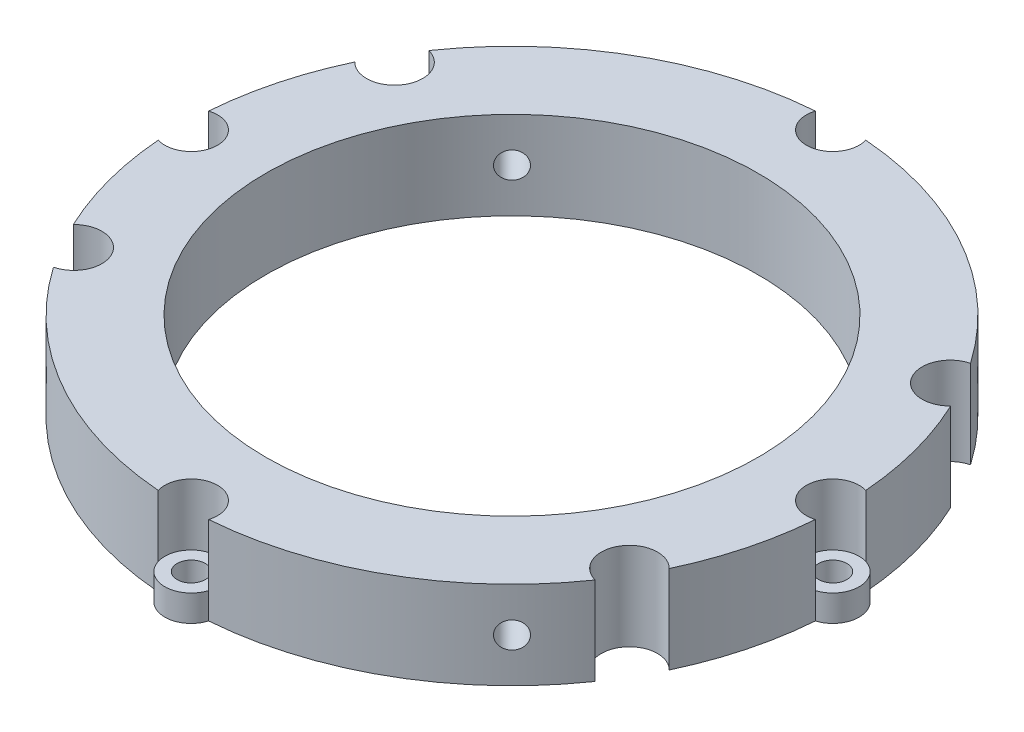
SolidWorks part; units mm, degrees
ref_plane "Ön Düzlem" through (0, 0, 0) normal (0, 0, 1) x (1, 0, 0)
ref_plane "Üst Düzlem" through (0, 0, 0) normal (0, 1, 0) x (1, 0, 0)
ref_plane "Sağ Düzlem" through (0, 0, 0) normal (1, 0, 0) x (0, 0, -1)
sketch "Çizim2" plane through (0, 0, 0) normal (0, 1, 0) x (1, 0, 0)
  arc A0 (-37.3801, -2.868) -> (-33.8981, -16.013) centre (0, 0) ccw
  circle A1 centre (0, 0) radius 28
  arc A2 (37.3801, 2.868) -> (37.3801, -2.868) centre (36.5, 0) ccw
  arc A4 (2.868, -37.3801) -> (-2.868, -37.3801) centre (0, -36.5) ccw
  arc A6 (-37.3801, -2.868) -> (-37.3801, 2.868) centre (-36.5, 0) ccw
  arc A8 (-2.868, 37.3801) -> (2.868, 37.3801) centre (0, 36.5) ccw
  arc A10 (30.8167, 21.3501) -> (33.8981, 16.013) centre (31.6099, 18.25) ccw
  arc A11 (2.868, -37.3801) -> (30.8167, -21.3501) centre (0, 0) ccw
  arc A12 (30.8167, 21.3501) -> (2.868, 37.3801) centre (0, 0) ccw
  arc A13 (37.3801, 2.868) -> (33.8981, 16.013) centre (0, 0) ccw
  arc A14 (-2.868, 37.3801) -> (-30.8167, 21.3501) centre (0, 0) ccw
  arc A15 (33.8981, -16.013) -> (30.8167, -21.3501) centre (31.6099, -18.25) ccw
  arc A16 (33.8981, -16.013) -> (37.3801, -2.868) centre (0, 0) ccw
  arc A17 (-33.8981, 16.013) -> (-30.8167, 21.3501) centre (-31.6099, 18.25) ccw
  arc A18 (-30.8167, -21.3501) -> (-33.8981, -16.013) centre (-31.6099, -18.25) ccw
  arc A19 (-33.8981, 16.013) -> (-37.3801, 2.868) centre (0, 0) ccw
  arc A20 (-30.8167, -21.3501) -> (-2.868, -37.3801) centre (0, 0) ccw
  point P19 (0, 0)
  dimension "D1" = 4
  dimension "D2" = 36.5
  dimension "D3" = 36.5
extrude "Yükseklik-Ekstrüzyon5" add sketch "Çizim2" along normal blind 10
ref_axis "Eksen1" through (0, 31.9173, 0) along (0, -1, 0)
ref_plane "Düzlem1" through (0, 0, 0) normal (-0.7071, 0, 0.7071) x (0, -1, 0)
sketch "Çizim3" plane through (0, 0, 0) normal (-0.7071, 0, 0.7071) x (0.7071, 0, 0.7071)
  circle A0 centre (0, 5) radius 1.49
extrude "Kes-Ekstrüzyon1" cut sketch "Çizim3" against normal through all
pattern_circular "Dairesel Kaplama1" count 4 over 360 about axis through (0, 31.9173, 0) along (0, -1, 0) of "Kes-Ekstrüzyon1"
sketch "Çizim4" plane through (0, 0, 0) normal (0, 1, 0) x (1, 0, 0)
  circle A0 centre (-36.5, 0) radius 3
  circle A1 centre (-36.5, 0) radius 1.6
extrude "Yükseklik-Ekstrüzyon6" add sketch "Çizim4" along normal blind 3
pattern_circular "Dairesel Kaplama2" count 4 over 360 about axis through (0, 31.9173, 0) along (0, -1, 0) of "Yükseklik-Ekstrüzyon6"
